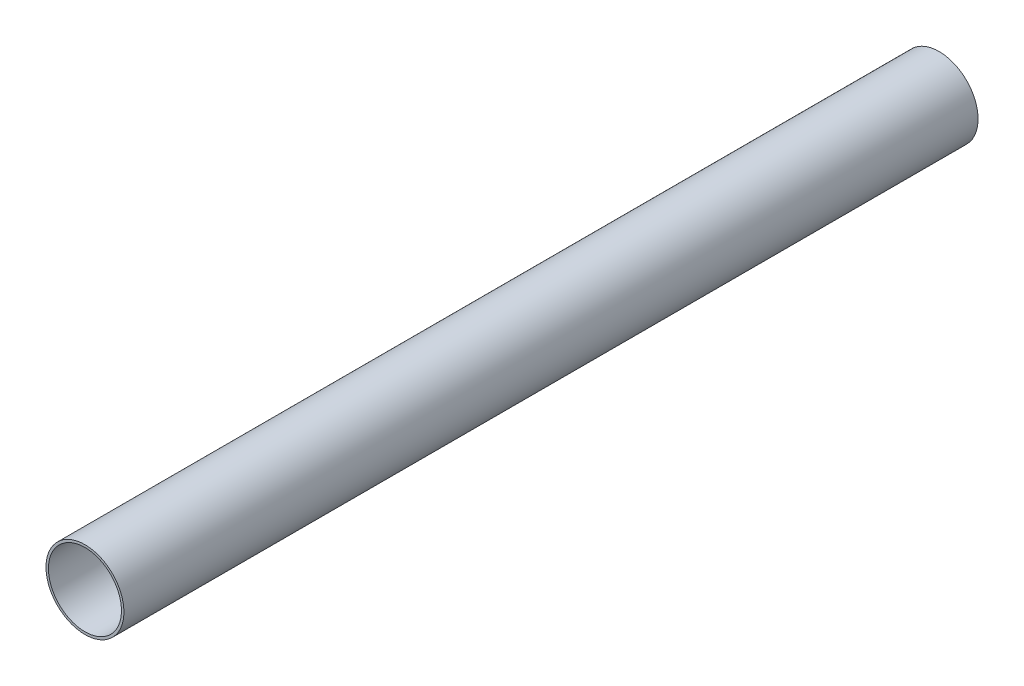
SolidWorks part; units mm, degrees
material "PC High Viscosity"
ref_plane "Front Plane" through (0, 0, 0) normal (0, 0, 1) x (1, 0, 0)
ref_plane "Top Plane" through (0, 0, 0) normal (0, 1, 0) x (1, 0, 0)
ref_plane "Right Plane" through (0, 0, 0) normal (1, 0, 0) x (0, 0, -1)
sketch "Sketch1" plane through (0, 0, 0) normal (0, 0, 1) x (1, 0, 0)
  circle A0 centre (0, 0) radius 23.8125
  circle A1 centre (0, 0) radius 25.4
  dimension "D1" = 50.8
  dimension "D2" = 47.625
extrude "Boss-Extrude1" add sketch "Sketch1" along normal mid plane 556.85
equation "\"D1@Boss-Extrude1\"=21.125in+3.625mm"
